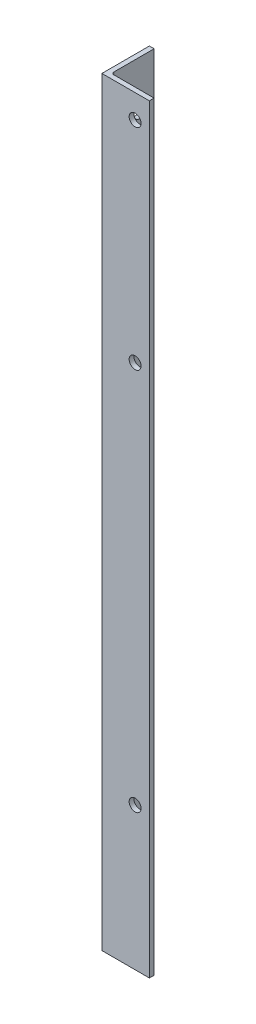
SolidWorks part; units mm, degrees
ref_plane "Front Plane" through (0, 0, 0) normal (0, 0, 1) x (1, 0, 0)
ref_plane "Top Plane" through (0, 0, 0) normal (0, 1, 0) x (1, 0, 0)
ref_plane "Right Plane" through (0, 0, 0) normal (1, 0, 0) x (0, 0, -1)
sketch "Sketch2" plane through (0, 0, 0) normal (0, 1, 0) x (1, 0, 0)
  line L0 (0, 31.75) -> (3.175, 31.75)
  line L1 (3.175, 31.75) -> (3.175, 4.7625)
  line L2 (4.7625, 3.175) -> (31.75, 3.175)
  line L3 (31.75, 3.175) -> (31.75, 0)
  line L4 (31.75, 0) -> (0, 0)
  line L5 (0, 0) -> (0, 31.75)
  arc A0 (3.175, 4.7625) -> (4.7625, 3.175) centre (4.7625, 4.7625) ccw
  point P9 (1.5875, 31.75)
  point P10 (31.75, 1.5875)
  dimension "D1" = 31.75
  dimension "D2" = 31.75
  dimension "D3" = 3.175
  dimension "D4" = 3.175
extrude "Boss-Extrude1" add sketch "Sketch2" along normal blind 508
sketch "LeftSideHoles-Sketch3" plane through (0, 0, 0) normal (0, 0, 1) x (1, 0, 0)
  line L0 (0, 0) -> (31.75, 0) construction
  line L1 (0, 508) -> (31.75, 508) construction
  line L3 (0, 508) -> (0, 0) construction
  circle A0 centre (22.225, 95.4) radius 4
  circle A6 centre (22.225, 492.125) radius 4
  circle A11 centre (22.225, 351.5849) radius 4
  point P24 (15.875, 0)
  dimension "D3" = 8
  dimension "D1" = 95.4
  dimension "D2" = 22.225
  dimension "D11" = 351.5849
  dimension "D8" = 15.875
  dimension "D4" = 492.125
sketch "BackSideHoles-Sketch4" plane through (0, 0, 0) normal (-1, 0, 0) x (0, 0, 1)
  line L0 (-31.75, 508) -> (0, 508) construction
  line L1 (0, 508) -> (0, 0) construction
  line L3 (-31.75, 0) -> (0, 0) construction
  circle A0 centre (-22.225, 95.4) radius 4
  circle A5 centre (-22.225, 476.25) radius 4
  dimension "D2" = 22.225
  dimension "D4" = 8
  dimension "D3" = 95.4
  dimension "D5" = 31.75
extrude "LeftSideHoles-Cut-Extrude1" cut sketch "LeftSideHoles-Sketch3" against normal blind 3.175
extrude "BackSideHoles-Cut-Extrude2" cut sketch "BackSideHoles-Sketch4" against normal blind 3.175
equation "\"RailThickness\"= .125in'Spec"
equation "\"VSWidth\"= 1.25in'Spec"
equation "\"VSHeight\"= 1.25in'Spec"
equation "\"VSLength\"= 20.0in"
equation "\"VSBottomSideRailHoleYFromBottomOfLowerRailYSValue\"= 95.4mm"
equation "\"FasteningHoleDiameter\"= .125in"
equation "\"VSTopSideRailHoleYFromEdge\"= \"TopRailHeight\" / 2"
equation "\"D1@LeftSideHoles-Sketch3\"=\"VSBottomSideRailHoleYFromBottomOfLowerRailYSValue\""
equation "\"D2@LeftSideHoles-Sketch3\"=\"FrameFastenerHoleOffsetFromSide\""
equation "\"D1@Boss-Extrude1\"=\"VSLength\""
equation "\"D4@BackSideHoles-Sketch4\"=\"FrameFastenerHoleDiameter\""
equation "\"VSMidSideRailHoleYFromV8TopOfMidSideRailYSValue\"= 351.58487mm"
equation "\"D1@Sketch2\"=\"VSHeight\""
equation "\"D2@Sketch2\"=\"VSWidth\""
equation "\"TopRailHeight\"= 1.25in"
equation "\"V1 BottomOfLowerRail\"= \"LegHeight\""
equation "\"D11@LeftSideHoles-Sketch3\"=\"VSMidSideRailHoleYFromV8TopOfMidSideRailYSValue\""
equation "\"D3@BackSideHoles-Sketch4\"=\"VSBottomSideRailHoleYFromBottomOfLowerRailYSValue\""
equation "\"D8@LeftSideHoles-Sketch3\"=\"VSTopSideRailHoleYFromEdge\""
equation "\"D5@Sketch2\"=\"FasteningHoleDiameter\""
equation "\"FrameFastenerHoleDiameter\"= 8mm"
equation "\"FrameFastenerHoleOffsetFromSide\"= \"VSWidth\" / 2 + \"GapBetweenVerticalSupportsAndRails\""
equation "\"D2@BackSideHoles-Sketch4\"=\"FrameFastenerHoleOffsetFromSide\""
equation "\"D3@LeftSideHoles-Sketch3\"=\"FrameFastenerHoleDiameter\""
equation "\"D5@BackSideHoles-Sketch4\"=\"TopBackRailHeight\"/2"
equation "\"TopBackRailHeight\"= 2.5in"
equation "\"GapBetweenVerticalSupportsAndRails\"= \"RailThickness\" * 2"
